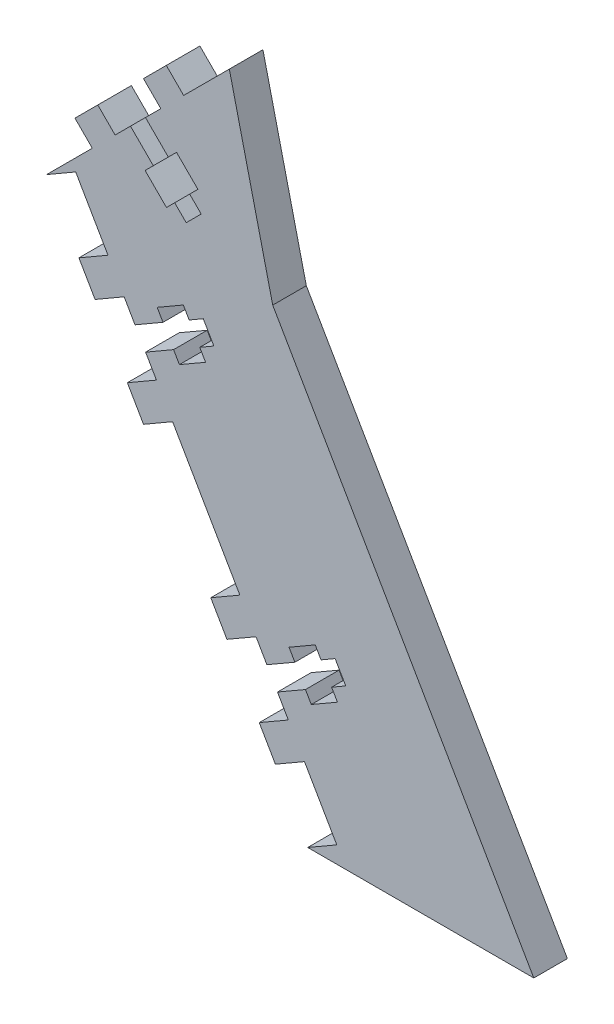
SolidWorks part; units mm, degrees
material "Acrylic (Blue)"
ref_plane "Front Plane" through (0, 0, 0) normal (0, 0, 1) x (1, 0, 0)
ref_plane "Top Plane" through (0, 0, 0) normal (0, 1, 0) x (1, 0, 0)
ref_plane "Right Plane" through (0, 0, 0) normal (1, 0, 0) x (0, 0, -1)
sketch "Sketch1" plane through (0, 0, 0) normal (0, 0, 1) x (1, 0, 0)
  line L0 (0, 0) -> (0, 304.4261) construction
  line L1 (0, 304.4261) -> (215.5261, 88.9)
  line L2 (215.5261, 88.9) -> (164.1997, 0)
  line L3 (164.1997, 0) -> (0, 0)
  line L4 (0, 304.4261) -> (-215.5261, 88.9)
  line L5 (-215.5261, 88.9) -> (-164.1997, 0)
  line L6 (-164.1997, 0) -> (0, 0)
  line L7 (-215.5261, 88.9) -> (215.5261, 88.9) construction
  line L8 (0, 304.4261) -> (3.5921, 308.0182) construction
  line L9 (3.5921, 308.0182) -> (219.1182, 92.4921) construction
  line L10 (219.1182, 92.4921) -> (215.5261, 88.9) construction
  line L11 (3.5921, 308.0182) -> (0, 311.6104) construction
  line L12 (0, 311.6104) -> (-219.1182, 92.4921) construction
  line L13 (-219.1182, 92.4921) -> (-215.5261, 88.9) construction
  line L14 (215.5261, 88.9) -> (219.9256, 86.36) construction
  line L15 (219.9256, 86.36) -> (168.5991, -2.54) construction
  line L16 (168.5991, -2.54) -> (164.1997, 0) construction
  line L17 (164.1997, 0) -> (164.1997, -12.7) construction
  line L18 (164.1997, -12.7) -> (-164.1997, -12.7) construction
  line L19 (-164.1997, -12.7) -> (-164.1997, 0) construction
  line L20 (-164.1997, 0) -> (-168.5991, -2.54) construction
  line L21 (-168.5991, -2.54) -> (-219.9256, 86.36) construction
  line L22 (-219.9256, 86.36) -> (-215.5261, 88.9) construction
  dimension "D1" = 304.8
  dimension "D2" = 120
  dimension "D3" = 88.9
  dimension "D4" = 5.08
  dimension "D5" = 12.7
extrude "Boss-Extrude1" add sketch "Sketch1" along normal blind 6.604
other "Move Face2" face at (107.7631, 196.6631, 3.302) offset 6.35 parameters "D1"=6.35
sketch "Sketch2" plane through (0, 0, 6.604) normal (0, 0, 1) x (1, 0, 0)
  line L0 (-119.7497, 0) -> (-171.0761, 88.9)
  line L1 (-164.1997, 0) -> (164.1997, 0) construction
  line L3 (-171.0761, 88.9) -> (-179.6051, 124.821)
  line L6 (-179.6051, 124.821) -> (4.4901, 308.9163)
  line L7 (4.4901, 308.9163) -> (218.8131, 94.5933)
  line L8 (218.8131, 94.5933) -> (164.1997, 0)
  line L9 (164.1997, 0) -> (-119.7497, 0)
  line L10 (4.4901, 308.9163) -> (-215.5261, 88.9) construction
  line L11 (-215.5261, 88.9) -> (-164.1997, 0) construction
  dimension "D1" = 88.9
  dimension "D2" = 44.45
  dimension "D3" = 12.7
  dimension "D4" = 12.7
sketch_block_instance "NUT_HOLE-25"
sketch_block "NUT_HOLE" parameters "D1"=6.35, "D2"=4.1656, "D3"=25.4, "D4"=4.826, "D5"=8.7376, "D6"=5.9436, "D7"=6.35, "D8"=20.32
extrude "Cut-Extrude1" cut sketch "Sketch2" against normal through all
sketch "Sketch3" plane through (0, 0, 6.604) normal (0, 0, 1) x (1, 0, 0)
  line L1 (-164.1997, 0) -> (-158.4805, 3.302)
  line L2 (-158.4805, 3.302) -> (-209.8069, 92.202)
  line L3 (-209.8069, 92.202) -> (-215.5261, 88.9)
  line L4 (-215.5261, 88.9) -> (-164.1997, 0)
  line L9 (-215.5261, 88.9) -> (-164.1997, 0) construction
  dimension "D3" = 6.604
extrude "Cut-Extrude2" cut sketch "Sketch3" against normal through all
sketch "Sketch4" plane through (0, 0, 6.604) normal (0, 0, 1) x (1, 0, 0)
  line L0 (-179.6051, 124.821) -> (-215.5261, 88.9) construction
  line L4 (-158.4805, 3.302) -> (-209.8069, 92.202) construction
  line L5 (-164.1997, 0) -> (-158.4805, 3.302) construction
  line L6 (-209.8069, 92.202) -> (-215.5261, 88.9) construction
  line B0 (-196.0655, 68.4012) -> (-190.5663, 71.5762) construction
  line B1 (-190.5663, 71.5762) -> (-189.4233, 69.5965) construction
  line B2 (-189.4233, 69.5965) -> (-184.2759, 72.5683) construction
  line B3 (-184.2759, 72.5683) -> (-185.4189, 74.548) construction
  line B4 (-185.4189, 74.548) -> (-182.6473, 76.1482) construction
  line B5 (-182.6473, 76.1482) -> (-184.7301, 79.7557) construction
  line B6 (-184.7301, 79.7557) -> (-187.5017, 78.1555) construction
  line B7 (-187.5017, 78.1555) -> (-188.6447, 80.1352) construction
  line B8 (-188.6447, 80.1352) -> (-193.7921, 77.1634) construction
  line B9 (-193.7921, 77.1634) -> (-192.6491, 75.1837) construction
  line B10 (-192.6491, 75.1837) -> (-198.1483, 72.0087) construction
  line B11 (-200.2819, 75.7042) -> (-204.4614, 73.2912) construction
  line B12 (-204.4614, 73.2912) -> (-207.6364, 78.7905) construction
  line B13 (-207.6364, 78.7905) -> (-203.4569, 81.2035) construction
  line B14 (-193.9319, 64.7057) -> (-198.1114, 62.2927) construction
  line B15 (-198.1114, 62.2927) -> (-194.9364, 56.7934) construction
  line B16 (-194.9364, 56.7934) -> (-190.7569, 59.2064) construction
  line B17 (-198.1483, 72.0087) -> (-196.0655, 68.4012) construction
  line B18 (-170.1391, 23.4953) -> (-164.6398, 26.6703) construction
  line B19 (-164.6398, 26.6703) -> (-163.4968, 24.6906) construction
  line B20 (-163.4968, 24.6906) -> (-158.3495, 27.6624) construction
  line B21 (-158.3495, 27.6624) -> (-159.4925, 29.6421) construction
  line B22 (-159.4925, 29.6421) -> (-156.7209, 31.2423) construction
  line B23 (-156.7209, 31.2423) -> (-158.8037, 34.8498) construction
  line B24 (-158.8037, 34.8498) -> (-161.5753, 33.2496) construction
  line B25 (-161.5753, 33.2496) -> (-162.7183, 35.2293) construction
  line B26 (-162.7183, 35.2293) -> (-167.8656, 32.2575) construction
  line B27 (-167.8656, 32.2575) -> (-166.7226, 30.2778) construction
  line B28 (-166.7226, 30.2778) -> (-172.2219, 27.1028) construction
  line B29 (-172.2219, 27.1028) -> (-174.3555, 30.7983) construction
  line B30 (-174.3555, 30.7983) -> (-178.5349, 28.3853) construction
  line B31 (-178.5349, 28.3853) -> (-181.7099, 33.8846) construction
  line B32 (-181.7099, 33.8846) -> (-177.5305, 36.2976) construction
  line B33 (-170.1391, 23.4953) -> (-168.0055, 19.7998) construction
  line B34 (-168.0055, 19.7998) -> (-172.1849, 17.3868) construction
  line B35 (-172.1849, 17.3868) -> (-169.0099, 11.8875) construction
  line B36 (-169.0099, 11.8875) -> (-164.8305, 14.3005) construction
  line B37 (-199.0384, 105.3878) -> (-194.5483, 100.8976) construction
  line B38 (-194.5483, 100.8976) -> (-196.1647, 99.2812) construction
  line B39 (-196.1647, 99.2812) -> (-191.962, 95.0784) construction
  line B40 (-191.962, 95.0784) -> (-190.3455, 96.6949) construction
  line B41 (-190.3455, 96.6949) -> (-188.0825, 94.4318) construction
  line B42 (-188.0825, 94.4318) -> (-185.137, 97.3774) construction
  line B43 (-185.137, 97.3774) -> (-187.4, 99.6404) construction
  line B44 (-187.4, 99.6404) -> (-185.7835, 101.2568) construction
  line B45 (-185.7835, 101.2568) -> (-189.9863, 105.4596) construction
  line B46 (-189.9863, 105.4596) -> (-191.6027, 103.8431) construction
  line B47 (-191.6027, 103.8431) -> (-196.0929, 108.3333) construction
  line B48 (-196.0929, 108.3333) -> (-193.0755, 111.3506) construction
  line B49 (-193.0755, 111.3506) -> (-196.488, 114.7631) construction
  line B50 (-196.488, 114.7631) -> (-191.9979, 119.2533) construction
  line B51 (-191.9979, 119.2533) -> (-188.5854, 115.8408) construction
  line B52 (-202.0558, 102.3704) -> (-205.4683, 105.7829) construction
  line B53 (-205.4683, 105.7829) -> (-209.9584, 101.2928) construction
  line B54 (-209.9584, 101.2928) -> (-206.5459, 97.8803) construction
  line B55 (-196.0929, 108.3333) -> (-199.0384, 105.3878) construction
  dimension "D1" = 12.7
  dimension "D4" = 12.7
  dimension "D5" = 12.7
sketch_block_instance "NUT_HOLE-23"
sketch_block_instance "NUT_HOLE-24"
sketch_block_instance "NUT_HOLE-27"
sketch "Sketch5" plane through (0, 0, 6.604) normal (0, 0, 1) x (1, 0, 0)
  line L0 (-199.0384, 105.3878) -> (-194.5483, 100.8976) construction
  line L1 (-191.6027, 103.8431) -> (-196.0929, 108.3333) construction
  line L2 (-189.9863, 105.4596) -> (-191.6027, 103.8431) construction
  line L3 (-185.7835, 101.2568) -> (-189.9863, 105.4596) construction
  line L4 (-187.4, 99.6404) -> (-185.7835, 101.2568) construction
  line L5 (-185.137, 97.3774) -> (-187.4, 99.6404) construction
  line L6 (-188.0825, 94.4318) -> (-185.137, 97.3774) construction
  line L7 (-191.962, 95.0784) -> (-190.3455, 96.6949) construction
  line L8 (-196.1647, 99.2812) -> (-191.962, 95.0784) construction
  line L9 (-194.5483, 100.8976) -> (-196.1647, 99.2812) construction
  line L10 (-199.0384, 105.3878) -> (-194.5483, 100.8976)
  line L11 (-191.6027, 103.8431) -> (-196.0929, 108.3333)
  line L12 (-189.9863, 105.4596) -> (-191.6027, 103.8431)
  line L13 (-185.7835, 101.2568) -> (-189.9863, 105.4596)
  line L14 (-187.4, 99.6404) -> (-185.7835, 101.2568)
  line L15 (-185.137, 97.3774) -> (-187.4, 99.6404)
  line L16 (-188.0825, 94.4318) -> (-185.137, 97.3774)
  line L17 (-191.962, 95.0784) -> (-190.3455, 96.6949)
  line L18 (-196.1647, 99.2812) -> (-191.962, 95.0784)
  line L19 (-194.5483, 100.8976) -> (-196.1647, 99.2812)
  line L20 (-196.0929, 108.3333) -> (-199.0384, 105.3878)
  line L42 (-190.3455, 96.6949) -> (-188.0825, 94.4318) construction
  line L44 (-190.3455, 96.6949) -> (-188.0825, 94.4318)
  line L88 (-193.7921, 77.1634) -> (-192.6491, 75.1837) construction
  line L89 (-188.6447, 80.1352) -> (-193.7921, 77.1634) construction
  line L90 (-184.7301, 79.7557) -> (-187.5017, 78.1555) construction
  line L91 (-187.5017, 78.1555) -> (-188.6447, 80.1352) construction
  line L92 (-182.6473, 76.1482) -> (-184.7301, 79.7557) construction
  line L93 (-185.4189, 74.548) -> (-182.6473, 76.1482) construction
  line L94 (-184.2759, 72.5683) -> (-185.4189, 74.548) construction
  line L95 (-189.4233, 69.5965) -> (-184.2759, 72.5683) construction
  line L96 (-190.5663, 71.5762) -> (-189.4233, 69.5965) construction
  line L97 (-196.0655, 68.4012) -> (-190.5663, 71.5762) construction
  line L98 (-192.6491, 75.1837) -> (-198.1483, 72.0087) construction
  line L99 (-193.7921, 77.1634) -> (-192.6491, 75.1837)
  line L100 (-188.6447, 80.1352) -> (-193.7921, 77.1634)
  line L101 (-184.7301, 79.7557) -> (-187.5017, 78.1555)
  line L102 (-187.5017, 78.1555) -> (-188.6447, 80.1352)
  line L103 (-182.6473, 76.1482) -> (-184.7301, 79.7557)
  line L104 (-185.4189, 74.548) -> (-182.6473, 76.1482)
  line L105 (-184.2759, 72.5683) -> (-185.4189, 74.548)
  line L106 (-189.4233, 69.5965) -> (-184.2759, 72.5683)
  line L107 (-190.5663, 71.5762) -> (-189.4233, 69.5965)
  line L108 (-196.0655, 68.4012) -> (-190.5663, 71.5762)
  line L109 (-192.6491, 75.1837) -> (-198.1483, 72.0087)
  line L110 (-164.6398, 26.6703) -> (-163.4968, 24.6906) construction
  line L111 (-170.1391, 23.4953) -> (-164.6398, 26.6703) construction
  line L112 (-167.8656, 32.2575) -> (-166.7226, 30.2778) construction
  line L113 (-166.7226, 30.2778) -> (-172.2219, 27.1028) construction
  line L114 (-162.7183, 35.2293) -> (-167.8656, 32.2575) construction
  line L115 (-161.5753, 33.2496) -> (-162.7183, 35.2293) construction
  line L116 (-158.8037, 34.8498) -> (-161.5753, 33.2496) construction
  line L117 (-156.7209, 31.2423) -> (-158.8037, 34.8498) construction
  line L118 (-159.4925, 29.6421) -> (-156.7209, 31.2423) construction
  line L119 (-158.3495, 27.6624) -> (-159.4925, 29.6421) construction
  line L120 (-163.4968, 24.6906) -> (-158.3495, 27.6624) construction
  line L121 (-164.6398, 26.6703) -> (-163.4968, 24.6906)
  line L122 (-170.1391, 23.4953) -> (-164.6398, 26.6703)
  line L123 (-167.8656, 32.2575) -> (-166.7226, 30.2778)
  line L124 (-166.7226, 30.2778) -> (-172.2219, 27.1028)
  line L125 (-162.7183, 35.2293) -> (-167.8656, 32.2575)
  line L126 (-161.5753, 33.2496) -> (-162.7183, 35.2293)
  line L127 (-158.8037, 34.8498) -> (-161.5753, 33.2496)
  line L128 (-156.7209, 31.2423) -> (-158.8037, 34.8498)
  line L129 (-159.4925, 29.6421) -> (-156.7209, 31.2423)
  line L130 (-158.3495, 27.6624) -> (-159.4925, 29.6421)
  line L131 (-163.4968, 24.6906) -> (-158.3495, 27.6624)
  line L134 (-198.1483, 72.0087) -> (-196.0655, 68.4012)
  line L135 (-172.2219, 27.1028) -> (-170.1391, 23.4953)
extrude "Cut-Extrude3" cut sketch "Sketch5" against normal through all
sketch "Sketch6" plane through (0, 0, 6.604) normal (0, 0, 1) x (1, 0, 0)
  line L0 (-193.0755, 111.3506) -> (-196.488, 114.7631) construction
  line L2 (-191.9979, 119.2533) -> (-188.5854, 115.8408) construction
  line L3 (-196.488, 114.7631) -> (-191.9979, 119.2533) construction
  line L4 (-205.4683, 105.7829) -> (-209.9584, 101.2928) construction
  line L5 (-202.0558, 102.3704) -> (-205.4683, 105.7829) construction
  line L6 (-209.9584, 101.2928) -> (-206.5459, 97.8803) construction
  line L7 (-193.0755, 111.3506) -> (-196.488, 114.7631)
  line L8 (-191.9979, 119.2533) -> (-188.5854, 115.8408)
  line L18 (-207.6364, 78.7905) -> (-203.4569, 81.2035) construction
  line L19 (-204.4614, 73.2912) -> (-207.6364, 78.7905) construction
  line L20 (-200.2819, 75.7042) -> (-204.4614, 73.2912) construction
  line L21 (-193.9319, 64.7057) -> (-198.1114, 62.2927) construction
  line L22 (-198.1114, 62.2927) -> (-194.9364, 56.7934) construction
  line L23 (-194.9364, 56.7934) -> (-190.7569, 59.2064) construction
  line L24 (-169.0099, 11.8875) -> (-164.8305, 14.3005) construction
  line L25 (-172.1849, 17.3868) -> (-169.0099, 11.8875) construction
  line L26 (-168.0055, 19.7998) -> (-172.1849, 17.3868) construction
  line L27 (-196.488, 114.7631) -> (-191.9979, 119.2533)
  line L28 (-205.4683, 105.7829) -> (-209.9584, 101.2928)
  line L29 (-202.0558, 102.3704) -> (-205.4683, 105.7829)
  line L30 (-209.9584, 101.2928) -> (-206.5459, 97.8803)
  line L31 (-188.5854, 115.8408) -> (-193.0755, 111.3506)
  line L32 (-206.5459, 97.8803) -> (-202.0558, 102.3704)
  line L39 (-174.3555, 30.7983) -> (-178.5349, 28.3853) construction
  line L40 (-178.5349, 28.3853) -> (-181.7099, 33.8846) construction
  line L41 (-181.7099, 33.8846) -> (-177.5305, 36.2976) construction
  line L51 (-207.6364, 78.7905) -> (-203.4569, 81.2035)
  line L52 (-204.4614, 73.2912) -> (-207.6364, 78.7905)
  line L53 (-200.2819, 75.7042) -> (-204.4614, 73.2912)
  line L54 (-193.9319, 64.7057) -> (-198.1114, 62.2927)
  line L55 (-198.1114, 62.2927) -> (-194.9364, 56.7934)
  line L56 (-194.9364, 56.7934) -> (-190.7569, 59.2064)
  line L57 (-169.0099, 11.8875) -> (-164.8305, 14.3005)
  line L58 (-172.1849, 17.3868) -> (-169.0099, 11.8875)
  line L59 (-168.0055, 19.7998) -> (-172.1849, 17.3868)
  line L60 (-174.3555, 30.7983) -> (-178.5349, 28.3853)
  line L61 (-178.5349, 28.3853) -> (-181.7099, 33.8846)
  line L62 (-181.7099, 33.8846) -> (-177.5305, 36.2976)
  line L66 (-203.4569, 81.2035) -> (-200.2819, 75.7042)
  line L67 (-193.9319, 64.7057) -> (-190.7569, 59.2064)
  line L69 (-177.5305, 36.2976) -> (-174.3555, 30.7983)
  line L70 (-168.0055, 19.7998) -> (-164.8305, 14.3005)
extrude "Boss-Extrude2" add sketch "Sketch6" against normal up to surface (6.604 mm away) up to face at (-180.2604, 66.4516, 0)
other "Move Face4" face at (-206.0489, 76.0408, 3.302) face at (-196.5239, 59.5431, 3.302) face at (-170.5974, 14.6372, 3.302) face at (-180.1224, 31.1349, 3.302) offset 1.778 parameters "D1"=1.778
other "Move Face3" [suppressed] offset 0.0508 parameters "D1"=0.0508
